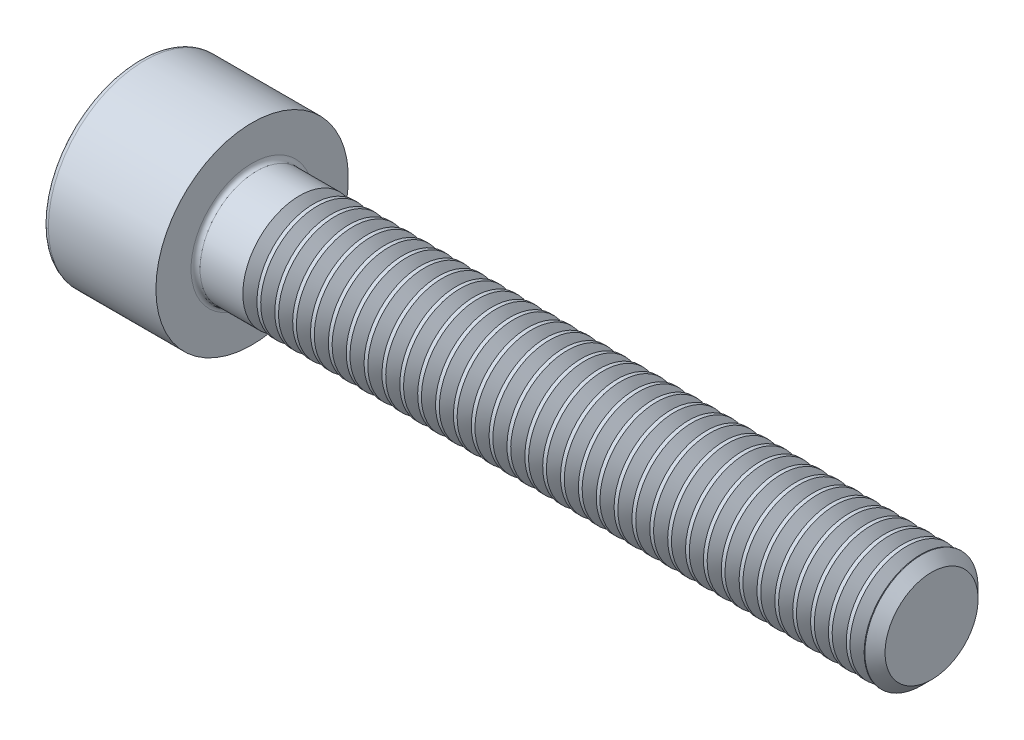
SolidWorks part; units mm, degrees
revolve "Base-Revolve" add sketch "BodySke"
sketch "BodySke" plane through (0, 0, 0) normal (0, 0, 1) x (1, 0, 0)
  line L0 (0, 0) -> (0, 4.25)
  line L1 (0, 4.25) -> (5, 4.25)
  line L2 (5, 4.25) -> (5, 2.5)
  line L3 (5, 2.5) -> (34.555, 2.5)
  line L4 (35, 2.055) -> (35, 0)
  line L5 (35, 0) -> (0, 0)
  line L6 (-31.75, 0) -> (127, 0) construction
  line L8 (35, 2.055) -> (34.555, 2.5)
  line L10 (35, -2.055) -> (34.555, -2.5) construction
  line L11 (5.8, 9.525) -> (5.8, 3.175) construction
  line L12 (5, 9.525) -> (5, 3.175) construction
  line L13 (-25, 9.525) -> (-25, 3.175) construction
  dimension "Diameter" = 5
  dimension "Head_dia" = 8.5
cosmetic thread "ThreadCosmetic" [suppressed]
fillet "Fillet1" radius 0.2 1 edges at (5, 0, 2.5)
fillet "Fillet2" radius 0.25 1 edges at (0, 0, 4.25)
ref_plane "Plane1" through (0, 0, 0) normal (0, 0, 1) x (1, 0, 0)
ref_plane "Plane2" through (0, 0, 0) normal (0, 1, 0) x (1, 0, 0)
ref_plane "Plane3" through (0, 0, 0) normal (1, 0, 0) x (0, 0, -1)
sketch "Sketch2" plane through (0, 0, 0) normal (0, 0, 1) x (1, 0, 0)
  line L0 (0, 2.042) -> (2.5, 2.042)
  line L1 (2.5, 2.042) -> (3.6789, 0)
  line L2 (-31.75, 0) -> (127, 0) construction
  line L3 (3.6789, 0) -> (0, 0)
  line L4 (0, 0) -> (0, 2.042)
  line L6 (0, 0) -> (47.625, 0) construction
  dimension "D1" = 2.042
  dimension "D2" = 60
revolve "Hex-PreBroach" cut sketch "Sketch2" angle 360 about L6
sketch "Sketch3" plane through (0, 0, 0) normal (-1, 0, 0) x (0, 0.5, 0.866)
  line L0 (1.1789, 2.042) -> (-1.1789, 2.042)
  line L1 (-1.1789, 2.042) -> (-2.3579, 0)
  line L2 (1.1789, 2.042) -> (2.3579, 0)
  line L3 (1.1789, -2.042) -> (2.3579, 0)
  line L4 (1.1789, -2.042) -> (-1.1789, -2.042)
  line L5 (-1.1789, -2.042) -> (-2.3579, 0)
  dimension "D1" = 2.042
  dimension "D2" = 2.042
extrude "Hex" cut sketch "Sketch3" against normal blind 2.5
sketch "ThdSchSke" plane through (0, 0, 0) normal (0, 0, 1) x (1, 0, 0)
  line L0 (7.4, -2.055) -> (7.0884, -2.5)
  line L1 (7.4, -2.055) -> (7.7116, -2.5)
  line L2 (7.7116, -2.5) -> (7.7116, -3.125)
  line L3 (-3.175, 0) -> (5.1513, 0) construction
  line L4 (0, 4) -> (0, -4) construction
  line L5 (7.7116, -3.125) -> (7.0884, -3.125)
  line L6 (7.0884, -3.125) -> (7.0884, -2.5)
  dimension "Diameter" = 5
  dimension "Thread_minor" = 4.11
  dimension "Start" = 7.4
revolve "ThreadSchematic" cut sketch "ThdSchSke" angle 360 about L3
pattern_linear "ThdSchPat" count 36 spacing 0.7886 along (1, 0, 0) of "ThreadSchematic"
equation "\"D2@Sketch3\" = \"Hex_size@Sketch3\" / 2"
equation "\"D1@Sketch3\" = \"Hex_size@Sketch3\" / 2"
equation "\"D1@Sketch2\" = \"Hex_size@Sketch3\" / 2"
equation "\"Thread_minor@ThreadCosmetic\"  =  \"Minor_dia@BodySke\""
equation "\"Depth@Sketch2\" =  \"Key_eng@Hex\""
equation "\"Thread_length@ThreadCosmetic\" = ((sgn( (\"Length@BodySke\" - \"Advance@BodySke\" * 3.0) - \"Thread_nom@BodySke\" )-1)*( (\"Length@BodySke\" - \"Advance@BodySke\" * 3.0) - \"Thread_nom@BodySke\" ))/-2+ \"Thread_nom@BodySke\""
equation "\"Thread_minor@ThdSchSke\" = \"Minor_dia@BodySke\""
equation "\"Diameter@ThdSchSke\" = \"Diameter@BodySke\""
equation "\"Overcut@ThdSchSke\" = \"Diameter@BodySke\" * 1.25"
equation "\"Start@ThdSchSke\" = \"Head_ht@BodySke\" + \"Length@BodySke\" - \"Thread_length@ThreadCosmetic\"  '---Non-countersunk---"
equation "\"Num_threads@ThdSchPat\" = int( \"Thread_length@ThreadCosmetic\" / \"Advance@BodySke\" + 0.999 )  + 1"
equation "\"Advance@ThdSchPat\" = \"Thread_length@ThreadCosmetic\" /  (\"Num_threads@ThdSchPat\" - 1) 'relax it"
equation "\"Num_threads@ThdSchPat\" = \"Num_threads@ThdSchPat\" - sgn( \"Num_threads@ThdSchPat\" - 1) '---chamfered tips only---"
